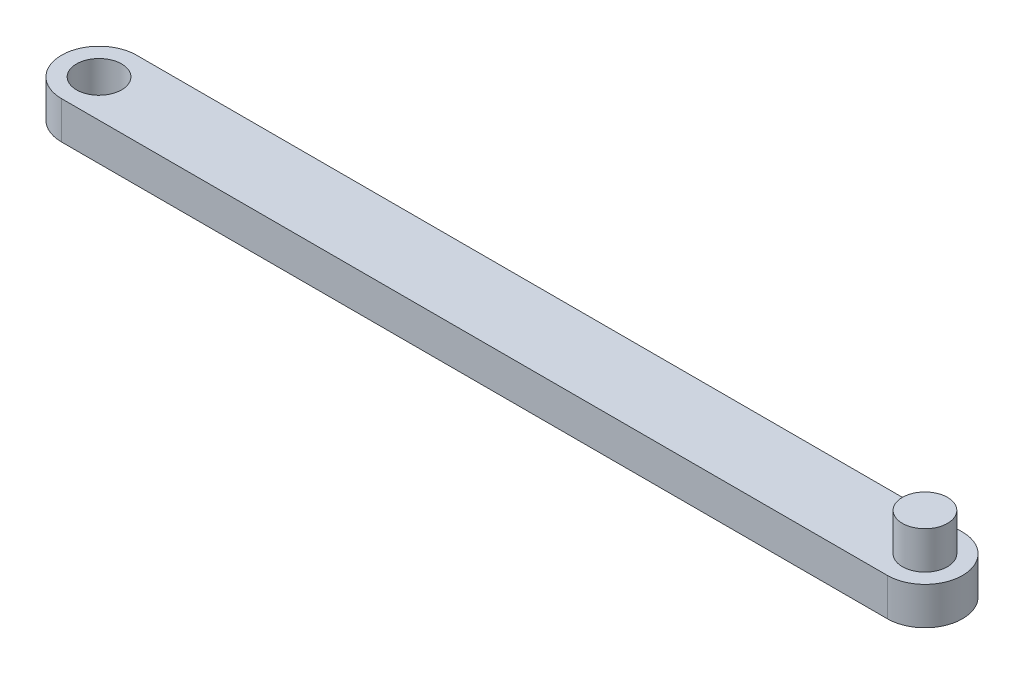
SolidWorks part; units mm, degrees
ref_plane "前视基准面" through (0, 0, 0) normal (0, 0, 1) x (1, 0, 0)
ref_plane "上视基准面" through (0, 0, 0) normal (0, 1, 0) x (1, 0, 0)
ref_plane "右视基准面" through (0, 0, 0) normal (1, 0, 0) x (0, 0, -1)
sketch "草图1" plane through (0, 0, 0) normal (0, 1, 0) x (1, 0, 0)
  line L0 (0, 0) -> (109.9, 0)
  line L2 (109.9, -10) -> (0, -10)
  arc A0 (0, 0) -> (0, -10) centre (0, -5) ccw
  arc A1 (109.9, -10) -> (109.9, 0) centre (109.9, -5) ccw
  circle A2 centre (0, -5) radius 3
  dimension "D1" = 109.9
  dimension "D2" = 6
  dimension "D3" = 5
extrude "凸台-拉伸1" add sketch "草图1" along normal blind 5
sketch "草图2" plane through (0, 5, 0) normal (0, 1, 0) x (1, 0, 0)
  circle A0 centre (109.9, -5) radius 3
extrude "凸台-拉伸2" add sketch "草图2" along normal blind 5
